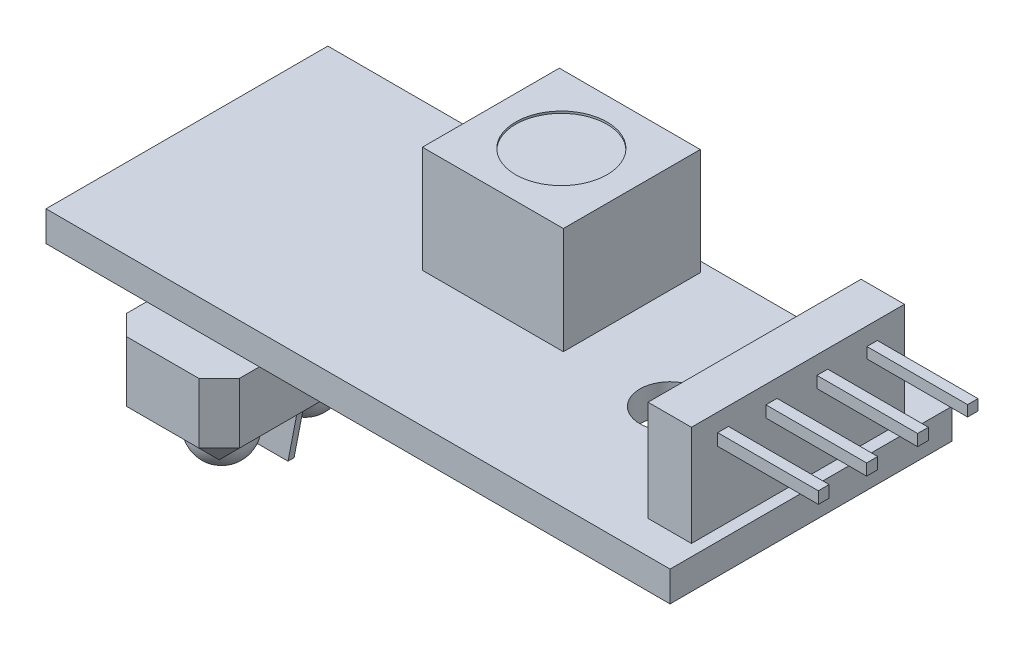
SolidWorks part; units mm, degrees
ref_plane "Front" through (0, 0, 0) normal (0, 0, 1) x (1, 0, 0)
ref_plane "Top" through (0, 0, 0) normal (0, 1, 0) x (1, 0, 0)
ref_plane "Right" through (0, 0, 0) normal (1, 0, 0) x (0, 0, -1)
sketch "草圖1" plane through (0, 0, 0) normal (0, 1, 0) x (1, 0, 0)
  line L0 (31, 0) -> (0, 0) construction
  line L1 (0, -7) -> (31, -7)
  line L2 (0, -7) -> (0, 7)
  line L3 (0, 7) -> (31, 7)
  line L4 (31, -7) -> (31, 7)
  dimension "D1" = 14
  dimension "D2" = 31
extrude "填料-伸長1" add sketch "草圖1" along normal blind 1.5
sketch "草圖2" plane through (0, 1.5, 0) normal (0, 1, 0) x (1, 0, 0)
  line L1 (12, 6.5) -> (19, 6.5)
  line L2 (12, 6.5) -> (12, -0.3)
  line L3 (12, -0.3) -> (19, -0.3)
  line L4 (19, 6.5) -> (19, -0.3)
  line L5 (31, 7) -> (0, 7) construction
  line L6 (0, 7) -> (0, -7) construction
  dimension "D1" = 6.8
  dimension "D2" = 7
  dimension "D3" = 0.5
  dimension "D4" = 12
extrude "填料-伸長2" add sketch "草圖2" along normal blind 5.3 separate body
sketch "草圖3" plane through (0, 1.5, 0) normal (0, 1, 0) x (1, 0, 0)
  line L1 (28.2749, 5.2139) -> (30.4297, 5.2139)
  line L2 (28.2749, 5.2139) -> (28.2749, -5.3678)
  line L3 (28.2749, -5.3678) -> (30.4297, -5.3678)
  line L4 (30.4297, 5.2139) -> (30.4297, -5.3678)
extrude "填料-伸長3" add sketch "草圖3" along normal blind 5 separate body
sketch "草圖5" plane through (30.4297, 0, 0) normal (1, 0, 0) x (0, 0, -1)
  line L1 (-4.063, 5.6149) -> (-3.5286, 5.6149)
  line L2 (-4.063, 5.6149) -> (-4.063, 5.0288)
  line L3 (-4.063, 5.0288) -> (-3.5286, 5.0288)
  line L4 (-3.5286, 5.6149) -> (-3.5286, 5.0288)
  line L5 (-1.6668, 5.6149) -> (-1.1152, 5.6149)
  line L6 (-1.6668, 5.6149) -> (-1.6668, 5.046)
  line L7 (-1.6668, 5.046) -> (-1.1152, 5.046)
  line L8 (-1.1152, 5.6149) -> (-1.1152, 5.046)
  line L9 (0.8673, 5.6149) -> (1.4017, 5.6149)
  line L10 (0.8673, 5.6149) -> (0.8673, 5.046)
  line L11 (0.8673, 5.046) -> (1.4017, 5.046)
  line L12 (1.4017, 5.6149) -> (1.4017, 5.046)
  line L13 (3.3496, 5.6149) -> (3.8668, 5.6149)
  line L14 (3.3496, 5.6149) -> (3.3496, 5.0805)
  line L15 (3.3496, 5.0805) -> (3.8668, 5.0805)
  line L16 (3.8668, 5.6149) -> (3.8668, 5.0805)
extrude "填料-伸長4" add sketch "草圖5" along normal blind 5
sketch "草圖6" plane through (0, 0, 0) normal (0, -1, 0) x (1, 0, 0)
  line L0 (0, -7) -> (0, 7) construction
  line L1 (1, -5) -> (6.6, -5)
  line L2 (1, -5) -> (1, 5)
  line L3 (1, 5) -> (6.6, 5)
  line L4 (6.6, -5) -> (6.6, 5)
  line L5 (31, -7) -> (0, -7) construction
  line L6 (0, 7) -> (31, 7) construction
  dimension "D1" = 1
  dimension "D2" = 2
  dimension "D3" = 2
  dimension "D4" = 5.6
extrude "填料-伸長5" add sketch "草圖6" along normal blind 4 from offset 4 separate body
sketch "草圖7" plane through (0, 0, 0) normal (0, -1, 0) x (1, 0, 0)
  line L1 (2.1643, 2.8635) -> (2.7643, 2.8635)
  line L2 (2.1643, 2.8635) -> (2.1643, 2.2635)
  line L3 (2.1643, 2.2635) -> (2.7643, 2.2635)
  line L4 (2.7643, 2.8635) -> (2.7643, 2.2635)
  line L5 (4.7968, 2.905) -> (5.3968, 2.905)
  line L6 (4.7968, 2.905) -> (4.7968, 2.305)
  line L7 (4.7968, 2.305) -> (5.3968, 2.305)
  line L8 (5.3968, 2.905) -> (5.3968, 2.305)
  line L9 (2.2887, -2.1527) -> (2.8887, -2.1527)
  line L10 (2.2887, -2.1527) -> (2.2887, -2.7527)
  line L11 (2.2887, -2.7527) -> (2.8887, -2.7527)
  line L12 (2.8887, -2.1527) -> (2.8887, -2.7527)
  line L13 (4.8175, -2.1112) -> (5.4175, -2.1112)
  line L14 (4.8175, -2.1112) -> (4.8175, -2.7112)
  line L15 (4.8175, -2.7112) -> (5.4175, -2.7112)
  line L16 (5.4175, -2.1112) -> (5.4175, -2.7112)
  dimension "D1" = 0.6
  dimension "D2" = 0.6
  dimension "D3" = 0.6
  dimension "D4" = 0.6
  dimension "D5" = 0.6
  dimension "D6" = 0.6
  dimension "D7" = 0.6
  dimension "D8" = 0.6
extrude "填料-伸長6" add sketch "草圖7" along normal up to next separate body
chamfer "導角1" distance 1 angle 45 6 edges at (3.8, -8, 5) (1, -6, 5) (1, -8, 0) (3.8, -8, -5) (6.6, -8, 0) (6.6, -6, 5)
sketch "草圖8" plane through (0, 1.5, 0) normal (0, 1, 0) x (1, 0, 0)
  line L0 (0, 0) -> (24, 0) construction
  circle A0 centre (24, 0) radius 1.5
  dimension "D1" = 3
  dimension "D2" = 24
extrude "除料-伸長1" cut sketch "草圖8" against normal blind 3
sketch "草圖9" plane through (0, -8, 0) normal (0, -1, 0) x (1, 0, 0)
  line L1 (2, 0.15) -> (5.6, 0.15)
  line L2 (2, 0.15) -> (2, -0.15)
  line L3 (2, -0.15) -> (5.6, -0.15)
  line L4 (5.6, 0.15) -> (5.6, -0.15)
  line L6 (0, 0) -> (2, 0) construction
  line L7 (2, 4) -> (2, -4) construction
  dimension "D1" = 0.3
  dimension "D2" = 3.6
extrude "填料-伸長7" add sketch "草圖9" along normal blind 2.2
chamfer "導角2" distance 2.2 angle 11 2 edges at (5.6, -10.2, 0) (2, -10.2, 0) first distance on face at (5.6, -9.1, 0) first distance on face at (2, -9.1, 0)
ref_plane "平面1" through (3.8, 0, 0) normal (-1, 0, 0) x (0, 0, 1)
sketch "草圖10" plane through (3.8, 0, 0) normal (-1, 0, 0) x (0, 0, 1)
  line L0 (-2.075, -8) -> (-2.075, -9.8)
  line L3 (-0.15, -8) -> (-4, -8) construction
  line L4 (-3.475, -8.4) -> (-3.475, -8)
  line L5 (-3.475, -8) -> (-2.075, -8)
  arc A0 (-2.075, -9.8) -> (-3.475, -8.4) centre (-2.075, -8.4) cw
  dimension "D1" = 1.8
  dimension "D2" = 1.4
revolve "旋轉1" add sketch "草圖10" angle 360 about L0
sketch "草圖11" plane through (3.8, 0, 0) normal (-1, 0, 0) x (0, 0, 1)
  line L0 (2.075, -8) -> (2.075, -9.8)
  line L3 (3.475, -8.4) -> (3.475, -8)
  line L4 (4, -8) -> (0.15, -8) construction
  line L5 (3.475, -8) -> (2.075, -8)
  arc A0 (2.075, -9.8) -> (3.475, -8.4) centre (2.075, -8.4) ccw
  dimension "D1" = 1.8
  dimension "D2" = 1.4
revolve "旋轉2" add sketch "草圖11" angle 360 about L0
sketch "草圖12" plane through (0, 6.8, 0) normal (0, 1, 0) x (1, 0, 0)
  circle A0 centre (15.5, 3.1) radius 2.2703
extrude "除料-伸長2" cut sketch "草圖12" against normal blind 0.1
